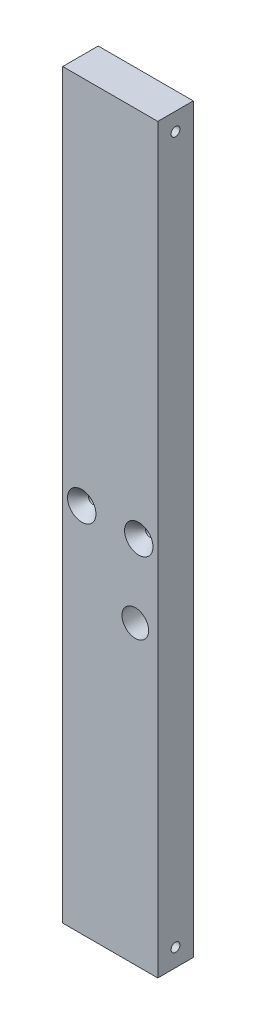
SolidWorks part; units mm, degrees
material "Beech"
ref_plane "Front Plane" through (0, 0, 0) normal (0, 0, 1) x (1, 0, 0)
ref_plane "Top Plane" through (0, 0, 0) normal (0, 1, 0) x (1, 0, 0)
ref_plane "Right Plane" through (0, 0, 0) normal (1, 0, 0) x (0, 0, -1)
sketch "Sketch1" plane through (0, 0, 0) normal (0, 0, 1) x (1, 0, 0)
  line L1 (-6.0809, 0) -> (-40.0809, 0) construction
  line L2 (-40.0809, -132.7) -> (-6.0809, -132.7)
  line L3 (-40.0809, -132.7) -> (-40.0809, 132.7)
  line L5 (-6.0809, -132.7) -> (-6.0809, 132.7)
  line L6 (-40.0809, 132.7) -> (-6.0809, 132.7)
  dimension "D1" = 34
  dimension "D2" = 12.7
extrude "Boss-Extrude1" add sketch "Sketch1" against normal blind 12.7
hole_wizard "3/8 (0.375) Diameter Hole1" positions "Sketch2" profile "Sketch3" hole size "3/8" standard "ANSI Inch" end condition through all
sketch "Sketch2" plane through (0, 0, 0) normal (0, 0, 1) x (1, 0, 0)
  point P0 (-14.118, -26.7327)
sketch "Sketch3" plane through (-14.118, -26.7327, 0) normal (1, 0, 0) x (0, -1, 0)
  line L0 (0, 0) -> (0, 12.7)
  line L1 (0, 12.7) -> (4.7625, 12.7)
  line L2 (4.7625, 12.7) -> (4.7625, 0)
  line L5 (4.7625, 0) -> (0, 0)
  line L11 (0, -6.35) -> (0, 107.95) construction
  dimension "Thru Hole Dia." = 9.525
  dimension "Thru Hole Depth" = 12.7
hole_wizard "Hole1" positions "Sketch4" profile "Sketch5" legacy
sketch "Sketch4" plane through (12.9191, 0, 66.1243) normal (1, 0, 0) x (0, -1, 0)
  line L21 (0, 20.1243) -> (0, 66.1243) construction
  point P37 (126.35, 72.4743)
  point P42 (146.0833, -84.8257)
  point P44 (172.1667, -84.8257)
  point P63 (126.35, -54.3757)
  point P65 (126.35, 42.0243)
  point P76 (-172.1667, -84.8257)
  point P77 (-146.0833, -84.8257)
  point P78 (-126.35, -54.3757)
  point P79 (-126.35, 42.0243)
  point P80 (-126.35, 72.4743)
sketch "Sketch5" plane through (12.9191, -126.35, -6.35) normal (0, 1, 0) x (0, 0, -1)
  line L0 (0, 0) -> (0, 32.7039)
  line L1 (0, 32.7039) -> (1.5875, 31.75)
  line L2 (1.5875, 31.75) -> (1.5875, 4.0177)
  line L3 (1.5875, 4.0177) -> (5.08, 0)
  line L4 (5.08, 0) -> (0, 0)
  line L5 (0, -14.3089) -> (0, 102.4216) construction
  line L6 (0, 32.7039) -> (-1.5875, 31.75) construction
  line L7 (-1.5875, 4.0177) -> (-5.08, 0) construction
  dimension "Diameter" = 3.175
  dimension "Depth" = 31.75
  dimension "C-Sink Diameter" = 10.16
  dimension "C-Sink Angle" = 82
  dimension "Drill Angle" = 118
hole_wizard "Hole3" positions "Sketch7" profile "Sketch8" legacy
sketch "Sketch7" plane through (-195.3677, 0, 0) normal (0, 0, 1) x (0, -1, 0)
  line L0 (0, 155.2867) -> (0, 189.2867) construction
  line L9 (0, 189.2867) -> (0, 182.4867)
  line L10 (0, 182.4867) -> (0, 175.6867)
  line L11 (0, 175.6867) -> (0, 168.8867)
  line L12 (0, 168.8867) -> (0, 162.0867)
  line L13 (0, 162.0867) -> (0, 155.2867)
  point P26 (0, 182.4867)
  point P32 (0, 162.0867)
sketch "Sketch8" plane through (-33.2809, 0, 0) normal (1, 0, 0) x (0, -1, 0)
  line L0 (0, 0) -> (0, 32.7039)
  line L1 (0, 32.7039) -> (1.5875, 31.75)
  line L2 (1.5875, 31.75) -> (1.5875, 4.0177)
  line L3 (1.5875, 4.0177) -> (5.08, 0)
  line L4 (5.08, 0) -> (0, 0)
  line L5 (0, -14.3089) -> (0, 102.4216) construction
  line L6 (0, 32.7039) -> (-1.5875, 31.75) construction
  line L7 (-1.5875, 4.0177) -> (-5.08, 0) construction
  dimension "Diameter" = 3.175
  dimension "Depth" = 31.75
  dimension "C-Sink Diameter" = 10.16
  dimension "C-Sink Angle" = 82
  dimension "Drill Angle" = 118
hole_wizard "Hole4" positions "Sketch9" profile "Sketch10" legacy
sketch "Sketch9" plane through (-52.7809, 0, 66.1243) normal (-1, 0, 0) x (0, 1, 0)
  line L12 (0, 0) -> (0, 66.1243) construction
  line L17 (120, -84.8257) -> (217.3, -84.8257) construction
  line L21 (-217.3, -84.8257) -> (-120, -84.8257) construction
  point P0 (-207.775, 244.1214)
  point P3 (-207.775, 136.589)
  point P6 (-207.775, 48.5243)
  point P9 (-185.55, -84.8257)
  point P12 (-151.75, -84.8257)
  point P15 (-94.6, 72.4743)
  point P21 (94.6, 72.4743)
  point P24 (151.75, -84.8257)
  point P27 (185.55, -84.8257)
  point P30 (207.775, 48.5243)
  point P33 (207.775, 136.589)
  point P36 (207.775, 244.1214)
  point P39 (166.7958, 213.0704)
  point P42 (40.9792, 213.0704)
  point P45 (-40.9792, 213.0704)
  point P48 (-166.7958, 213.0704)
  point P51 (0, 104.2243)
  point P54 (0, 213.0704)
  point P57 (0, 323.4664)
  point P80 (-126.35, 34.5243)
  point P82 (-126.35, -46.8757)
  point P96 (126.35, -46.8757)
  point P97 (126.35, 34.5243)
  point P130 (0, 0)
  dimension "D4" = 31.75
  dimension "D5" = 31.75
sketch "Sketch10" plane through (-52.7809, -207.775, -177.9971) normal (0, 1, 0) x (0, 0, 1)
  line L0 (0, 0) -> (0, 32.7039)
  line L1 (0, 32.7039) -> (1.5875, 31.75)
  line L2 (1.5875, 31.75) -> (1.5875, 4.0177)
  line L3 (1.5875, 4.0177) -> (5.08, 0)
  line L4 (5.08, 0) -> (0, 0)
  line L5 (0, -14.3089) -> (0, 102.4216) construction
  line L6 (0, 32.7039) -> (-1.5875, 31.75) construction
  line L7 (-1.5875, 4.0177) -> (-5.08, 0) construction
  dimension "Diameter" = 3.175
  dimension "Depth" = 31.75
  dimension "C-Sink Diameter" = 10.16
  dimension "C-Sink Angle" = 82
  dimension "Drill Angle" = 118
